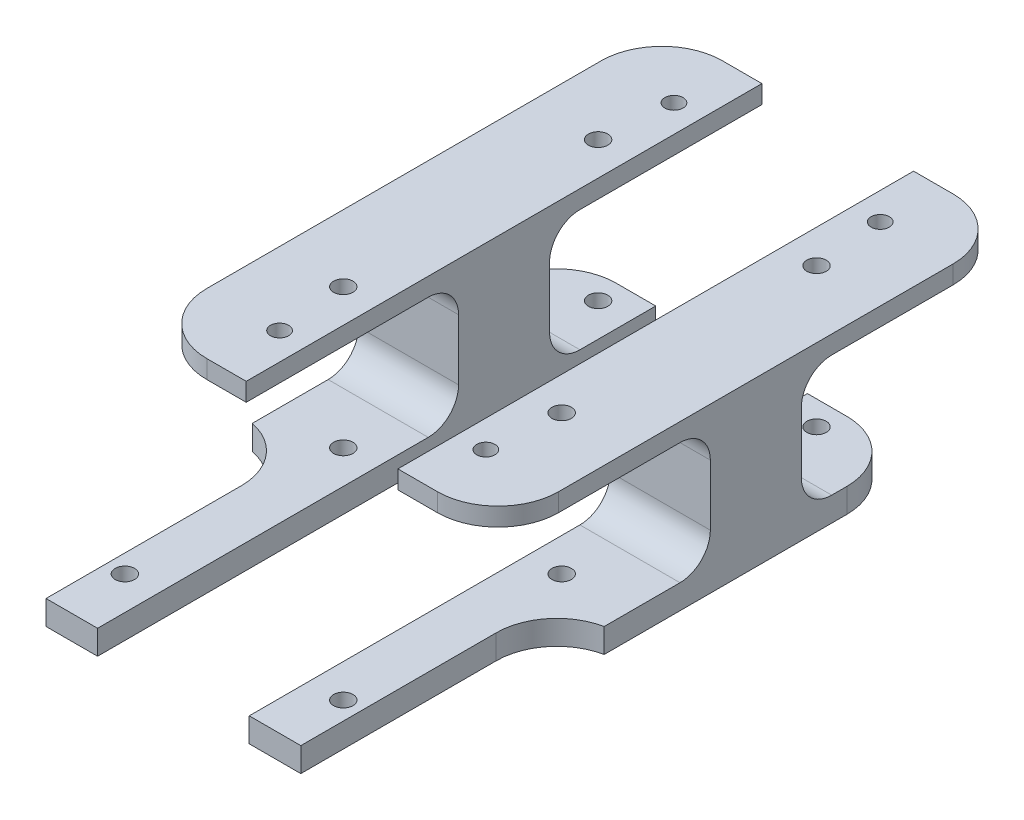
SolidWorks part; units mm, degrees
ref_plane "前视基准面" through (0, 0, 0) normal (0, 0, 1) x (1, 0, 0)
ref_plane "上视基准面" through (0, 0, 0) normal (0, 1, 0) x (1, 0, 0)
ref_plane "右视基准面" through (0, 0, 0) normal (1, 0, 0) x (0, 0, -1)
other "Configuration Table"
sketch "草图1" plane through (0, 0, 0) normal (0, 1, 0) x (1, 0, 0)
  line L1 (-29, -42.5) -> (29, -42.5)
  line L2 (-29, -42.5) -> (-29, 32.5)
  line L3 (-19, 42.5) -> (19, 42.5)
  line L4 (29, -42.5) -> (29, 32.5)
  line L5 (-29, -42.5) -> (29, 42.5) construction
  line L6 (-29, 42.5) -> (29, -42.5) construction
  line L11 (-17, -32.5) -> (17, 32.5) construction
  line L12 (-17, 32.5) -> (17, -32.5) construction
  circle A0 centre (17, 32.5) radius 1.5
  circle A1 centre (-17, 32.5) radius 1.5
  circle A2 centre (-17, -32.5) radius 1.5
  circle A3 centre (17, -32.5) radius 1.5
  arc A4 (29, 32.5) -> (19, 42.5) centre (19, 32.5) ccw
  arc A5 (-19, 42.5) -> (-29, 32.5) centre (-19, 32.5) ccw
  point P0 (0, 0)
  point P5 (0, 0)
  dimension "D5" = 3
  dimension "D6" = 3
  dimension "D7" = 3
  dimension "D8" = 3
  dimension "D9" = 10
  dimension "D1" = 85
  dimension "D2" = 58
  dimension "D3" = 65
  dimension "D4" = 34
extrude "凸台-拉伸1" add sketch "草图1" along normal blind 3
sketch "草图4" plane through (0, 0, 0) normal (0, -1, 0) x (1, 0, 0)
  line L1 (-29, -7.5) -> (29, -7.5)
  line L2 (-29, -7.5) -> (-29, 7.5)
  line L3 (-29, 7.5) -> (29, 7.5)
  line L4 (29, -7.5) -> (29, 7.5)
  line L5 (-29, -7.5) -> (29, 7.5) construction
  line L6 (-29, 7.5) -> (29, -7.5) construction
  line L7 (29, 42.5) -> (29, -32.5) construction
  point P0 (0, 0)
  dimension "D1" = 15
  dimension "D2" = 58
extrude "凸台-拉伸2" add sketch "草图4" along normal blind 20
sketch "草图5" plane through (0, -20, 0) normal (0, -1, 0) x (1, 0, 0)
  line L5 (-18, -21) -> (18, -21)
  line L6 (-18, -21) -> (-18, 21)
  line L7 (-21, 57) -> (21, 57)
  line L8 (21, 57) -> (21, 25)
  line L9 (-18, 21) -> (18, 21)
  line L10 (-29, -25) -> (29, -25)
  line L11 (-29, -25) -> (-29, 25)
  line L12 (-29, 25) -> (-21, 25)
  line L13 (29, -25) -> (29, 25)
  line L14 (18, -21) -> (18, 21)
  line L15 (-18, -21) -> (18, 21) construction
  line L16 (29, 42.5) -> (29, 7.5) construction
  line L17 (-18, 21) -> (18, -21) construction
  line L18 (21, 57) -> (-21, 57)
  line L19 (21, 57) -> (21, 67)
  line L20 (21, 67) -> (-21, 67)
  line L21 (21, 25) -> (29, 25)
  line L22 (-21, 25) -> (-21, 57)
  line L23 (-21, 57) -> (-21, 67)
  circle A4 centre (-18, -21) radius 1.6
  circle A5 centre (18, -21) radius 1.6
  circle A6 centre (18, 21) radius 1.6
  circle A7 centre (-18, 21) radius 1.6
  circle A8 centre (-18, 57) radius 1.6
  circle A9 centre (18, 57) radius 1.6
  point P0 (0, 0)
  point P1 (0, 0)
  point P8 (0, 0)
  line M1 (29, -7.5) -> (29, 7.5)
  line M2 (29, 7.5) -> (-29, 7.5)
  line M3 (-29, 7.5) -> (-29, -7.5)
  line M4 (-29, -7.5) -> (29, -7.5)
  dimension "D5" = 3.2
  dimension "D6" = 3.2
  dimension "D7" = 3.2
  dimension "D8" = 3.2
  dimension "D9" = 3.2
  dimension "D10" = 3.2
  dimension "D11" = 36
  dimension "D12" = 36
  dimension "D1" = 42
  dimension "D2" = 36
  dimension "D3" = 50
  dimension "D4" = 58
  dimension "D13" = 10
  dimension "D14" = 42
extrude "凸台-拉伸3" add sketch "草图5" along normal blind 4 contours A5 L5 A4 L6 L11 L10 L13 L14 M4 | L14 L6 M4 M2 | A5 L14 L6 A4 L5 M4 | L6 M4 M2 M3 | A9 L7 A8 L22 L12 L11 L6 A7 L9 A6 L14 L13 L21 L8 M2 | A7 L6 L14 A6 L9 M2 | L14 M4 M1 M2 | A9 L7 L19 L20 L23 A8
fillet "圆角1" radius 10 10 edges at (29, 1.5, 42.5) (-29, 1.5, 42.5) (-25, -20, 25) (25, -20, 25) (-25, -24, 25) (-21, -22, 25) (-29, -22, -25) (29, -22, -25) (25, -24, 25) (21, -22, 25)
sketch "草图6" plane through (0, -24, 0) normal (0, -1, 0) x (1, 0, 0)
  circle A0 centre (18, 21) radius 1.6
  circle A1 centre (18, -21) radius 1.6
  circle A2 centre (-18, -21) radius 1.6
  circle A3 centre (-18, 21) radius 1.6
  dimension "D1" = 3.2
  dimension "D2" = 3.2
extrude "切除-拉伸2" cut sketch "草图6" against normal blind 63
sketch "草图7" plane through (0, 3, 0) normal (0, 1, 0) x (1, 0, 0)
  line L1 (-12.5, -42.5) -> (12.5, -42.5)
  line L2 (-12.5, -42.5) -> (-12.5, 42.5)
  line L3 (-12.5, 42.5) -> (12.5, 42.5)
  line L4 (12.5, -42.5) -> (12.5, 42.5)
  line L5 (-12.5, -42.5) -> (12.5, 42.5) construction
  line L6 (-12.5, 42.5) -> (12.5, -42.5) construction
  line L7 (19, 42.5) -> (-19, 42.5) construction
  point P0 (0, 0)
  dimension "D1" = 85
  dimension "D2" = 25
extrude "切除-拉伸3" cut sketch "草图7" against normal blind 63
sketch "草图8" plane through (0, -20, 0) normal (0, 1, 0) x (1, 0, 0)
  line L1 (-12.5, -42.5) -> (12.5, -42.5)
  line L2 (-12.5, -42.5) -> (-12.5, -67)
  line L3 (-12.5, -67) -> (12.5, -67)
  line L4 (12.5, -42.5) -> (12.5, -67)
  line L5 (21, -67) -> (-21, -67) construction
  dimension "D1" = 24.5
  dimension "D2" = 25
extrude "切除-拉伸4" cut sketch "草图8" against normal blind 63
fillet "圆角2" radius 5 2 edges at (-20.75, 0, -7.5) (-20.75, 0, 7.5)
fillet "圆角3" radius 5 4 edges at (20.75, 0, 7.5) (20.75, 0, -7.5) (20.75, -20, -7.5) (20.75, -20, 7.5)
fillet "圆角4" radius 5 2 edges at (-20.75, -20, 7.5) (-20.75, -20, -7.5)
